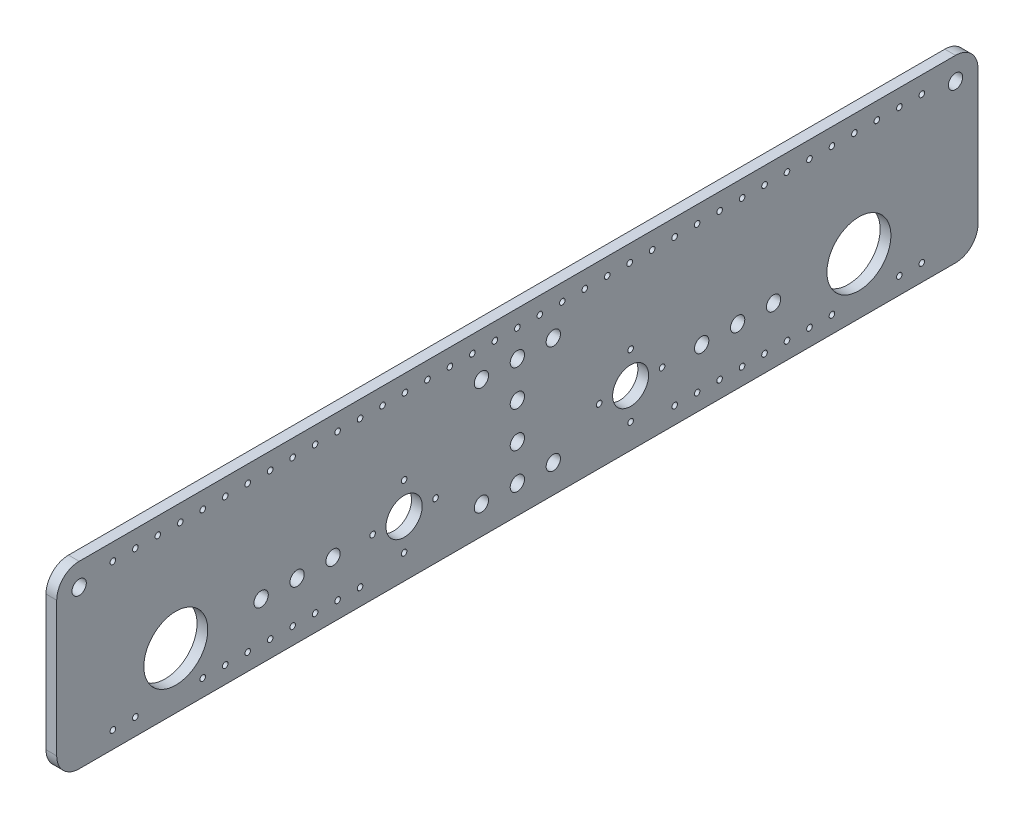
SolidWorks part; units mm, degrees
ref_plane "Front Plane" through (0, 0, 0) normal (0, 0, 1) x (1, 0, 0)
ref_plane "Top Plane" through (0, 0, 0) normal (0, 1, 0) x (1, 0, 0)
ref_plane "Right Plane" through (0, 0, 0) normal (1, 0, 0) x (0, 0, -1)
sketch "Sketch2" plane through (0, 0, 0) normal (1, 0, 0) x (0, 0, -1)
  line L0 (-23.4723, 28.6683) -> (-23.4723, -31.3317)
  line L1 (-13.4723, 38.6683) -> (376.5277, 38.6683)
  line L2 (-13.4723, -41.3317) -> (376.5277, -41.3317)
  line L3 (386.5277, 28.6683) -> (386.5277, -31.3317)
  circle A1 centre (29.5277, -16.3317) radius 14.225
  circle A2 centre (333.5277, -16.3317) radius 14.225
  arc A15 (-23.4723, 28.6683) -> (-13.4723, 38.6683) centre (-13.4723, 28.6683) cw
  arc A16 (-13.4723, -41.3317) -> (-23.4723, -31.3317) centre (-13.4723, -31.3317) cw
  arc A17 (386.5277, 28.6683) -> (376.5277, 38.6683) centre (376.5277, 28.6683) ccw
  arc A18 (376.5277, -41.3317) -> (386.5277, -31.3317) centre (376.5277, -31.3317) ccw
  circle A59 centre (181.5277, -28.7717) radius 3.18
  circle A60 centre (197.5277, -28.7717) radius 3.18
  circle A63 centre (197.5277, 19.2283) radius 3.18
  circle A64 centre (181.5277, -12.7717) radius 3.18
  circle A65 centre (181.5277, 3.2283) radius 3.18
  circle A66 centre (181.5277, 19.2283) radius 3.18
  circle A67 centre (165.5277, -28.7717) radius 3.18
  circle A68 centre (165.5277, 19.2283) radius 3.18
  circle A69 centre (197.5277, -12.7717) radius 3.18 [skipped]
  circle A70 centre (197.5277, 3.2283) radius 3.18 [skipped]
  circle A71 centre (-8.4723, 31.1683) radius 1.25 construction
  circle A150 centre (83.5027, -16.3317) radius 3.18
  circle A151 centre (279.5527, -16.3317) radius 3.18
  circle A152 centre (1.5277, 31.1683) radius 1.25
  circle A153 centre (11.5277, 31.1683) radius 1.25
  circle A154 centre (21.5277, 31.1683) radius 1.25
  circle A155 centre (31.5277, 31.1683) radius 1.25
  circle A156 centre (41.5277, 31.1683) radius 1.25
  circle A157 centre (51.5277, 31.1683) radius 1.25
  circle A158 centre (61.5277, 31.1683) radius 1.25
  circle A159 centre (71.5277, 31.1683) radius 1.25
  circle A160 centre (81.5277, 31.1683) radius 1.25
  circle A161 centre (91.5277, 31.1683) radius 1.25
  circle A162 centre (101.5277, 31.1683) radius 1.25
  circle A163 centre (111.5277, 31.1683) radius 1.25
  circle A164 centre (121.5277, 31.1683) radius 1.25
  circle A165 centre (131.5277, 31.1683) radius 1.25
  circle A166 centre (141.5277, 31.1683) radius 1.25
  circle A167 centre (151.5277, 31.1683) radius 1.25
  circle A168 centre (161.5277, 31.1683) radius 1.25
  circle A169 centre (171.5277, 31.1683) radius 1.25
  circle A170 centre (181.5277, 31.1683) radius 1.25
  circle A171 centre (191.5277, 31.1683) radius 1.25
  circle A172 centre (201.5277, 31.1683) radius 1.25
  circle A173 centre (211.5277, 31.1683) radius 1.25
  circle A174 centre (221.5277, 31.1683) radius 1.25
  circle A175 centre (231.5277, 31.1683) radius 1.25
  circle A176 centre (241.5277, 31.1683) radius 1.25
  circle A177 centre (251.5277, 31.1683) radius 1.25
  circle A178 centre (261.5277, 31.1683) radius 1.25
  circle A179 centre (271.5277, 31.1683) radius 1.25
  circle A180 centre (281.5277, 31.1683) radius 1.25
  circle A181 centre (291.5277, 31.1683) radius 1.25
  circle A182 centre (301.5277, 31.1683) radius 1.25
  circle A183 centre (311.5277, 31.1683) radius 1.25
  circle A184 centre (321.5277, 31.1683) radius 1.25
  circle A185 centre (331.5277, 31.1683) radius 1.25
  circle A186 centre (341.5277, 31.1683) radius 1.25
  circle A187 centre (351.5277, 31.1683) radius 1.25
  circle A188 centre (361.5277, 31.1683) radius 1.25
  circle A190 centre (1.5277, -33.8317) radius 1.25
  circle A191 centre (11.5277, -33.8317) radius 1.25
  circle A194 centre (41.5277, -33.8317) radius 1.25
  circle A195 centre (51.5277, -33.8317) radius 1.25
  circle A196 centre (61.5277, -33.8317) radius 1.25
  circle A197 centre (71.5277, -33.8317) radius 1.25
  circle A198 centre (81.5277, -33.8317) radius 1.25
  circle A199 centre (91.5277, -33.8317) radius 1.25
  circle A200 centre (101.5277, -33.8317) radius 1.25
  circle A201 centre (111.5277, -33.8317) radius 1.25
  circle A215 centre (251.5277, -33.8317) radius 1.25
  circle A216 centre (261.5277, -33.8317) radius 1.25
  circle A217 centre (271.5277, -33.8317) radius 1.25
  circle A218 centre (281.5277, -33.8317) radius 1.25
  circle A219 centre (291.5277, -33.8317) radius 1.25
  circle A220 centre (301.5277, -33.8317) radius 1.25
  circle A221 centre (311.5277, -33.8317) radius 1.25
  circle A222 centre (321.5277, -33.8317) radius 1.25
  circle A225 centre (351.5277, -33.8317) radius 1.25
  circle A226 centre (361.5277, -33.8317) radius 1.25
  circle A229 centre (181.5277, -33.8317) radius 1.25 [skipped]
  circle A230 centre (201.5277, -33.8317) radius 1.25 [skipped]
  circle A231 centre (161.5277, -33.8317) radius 1.25 [skipped]
  circle A232 centre (151.5277, -33.8317) radius 1.25 [skipped]
  circle A233 centre (141.5277, -33.8317) radius 1.25 [skipped]
  circle A234 centre (131.5277, -33.8317) radius 1.25 [skipped]
  circle A235 centre (171.5277, -33.8317) radius 1.25 [skipped]
  circle A236 centre (191.5277, -33.8317) radius 1.25 [skipped]
  circle A237 centre (211.5277, -33.8317) radius 1.25 [skipped]
  circle A238 centre (221.5277, -33.8317) radius 1.25 [skipped]
  circle A239 centre (231.5277, -33.8317) radius 1.25 [skipped]
  circle A240 centre (31.5277, -33.8317) radius 1.25 [skipped]
  circle A241 centre (21.5277, -33.8317) radius 1.25 [skipped]
  circle A242 centre (331.5277, -33.8317) radius 1.25 [skipped]
  circle A243 centre (341.5277, -33.8317) radius 1.25 [skipped]
  circle A245 centre (-13.4723, 28.6683) radius 3.18
  circle A247 centre (376.5277, 28.6683) radius 3.18
  circle A248 centre (371.5277, 31.1683) radius 1.25 [skipped]
  circle A249 centre (371.5277, -33.8317) radius 1.25 [skipped]
  circle A250 centre (-8.4723, -33.8317) radius 1.25 [skipped]
  circle A253 centre (99.5027, -16.3317) radius 3.18
  circle A254 centre (295.5527, -16.3317) radius 3.18
  circle A255 centre (67.5027, -16.3317) radius 3.18
  circle A256 centre (263.5527, -16.3317) radius 3.18
  circle A257 centre (121.5277, -33.8317) radius 1.25 [skipped]
  circle A260 centre (131.1277, -30.3317) radius 1.25
  circle A261 centre (145.1277, -16.3317) radius 1.25
  circle A262 centre (131.1277, -2.3317) radius 1.25
  circle A263 centre (117.1277, -16.3317) radius 1.25
  circle A264 centre (231.9277, -30.3317) radius 1.25
  circle A265 centre (217.9277, -16.3317) radius 1.25
  circle A266 centre (231.9277, -2.3317) radius 1.25
  circle A267 centre (245.9277, -16.3317) radius 1.25
  circle A268 centre (231.9277, -16.3317) radius 8
  circle A269 centre (131.1277, -16.3317) radius 8.0683
  circle A270 centre (241.5277, -33.8317) radius 1.25 [skipped]
  point P32 (-23.4723, 38.6683)
  point P35 (-23.4723, -41.3317)
  point P40 (386.5277, -41.3317)
  point P123 (181.5277, -41.3317)
  point P125 (0, 0)
  dimension "D3" = 25
  dimension "D7" = 10
  dimension "D8" = 10
  dimension "D9" = 10
  dimension "D10" = 10
  dimension "D11" = 7.5
  dimension "D13" = 12.56
  dimension "D1" = 80
  dimension "D2" = 410
  dimension "D4" = 53
  dimension "D5" = 25
  dimension "D6" = 53
  dimension "D12" = 15
  dimension "D14" = 205
  dimension "D15" = 2
  dimension "D16" = 4
  dimension "D17" = 2
  dimension "D18" = 39
  dimension "D19" = 2
  dimension "D22" = 2
  dimension "D23" = 2
extrude "Boss-Extrude1" add sketch "Sketch2" along normal blind 4.7625
